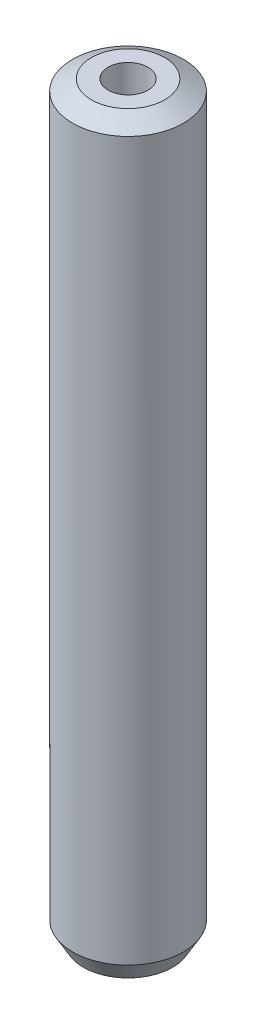
SolidWorks part; units mm, degrees
ref_plane "Front Plane" through (0, 0, 0) normal (0, 0, 1) x (1, 0, 0)
ref_plane "Top Plane" through (0, 0, 0) normal (0, 1, 0) x (1, 0, 0)
ref_plane "Right Plane" through (0, 0, 0) normal (1, 0, 0) x (0, 0, -1)
sketch "Sketch1" plane through (0, 0, 0) normal (0, 1, 0) x (1, 0, 0)
  circle A0 centre (0, 0) radius 17.5
  dimension "SHAFT_OD" = 35
extrude "Boss-Extrude1" add sketch "Sketch1" along normal blind 235.9055
sketch "Sketch2" plane through (0, 0, 0) normal (0, 1, 0) x (1, 0, 0)
  circle A0 centre (0, 0) radius 6.2877
  dimension "BORE_D" = 12.5755
extrude "Cut-Extrude1" cut sketch "Sketch2" along normal through all
chamfer "Chamfer1" distance 3.4248 angle 60 2 edges at (0, 235.9055, 17.5) (0, 0, 17.5) first distance on face at (0, 235.9055, 17.5) first distance on face at (0, 0, 6.2877)
